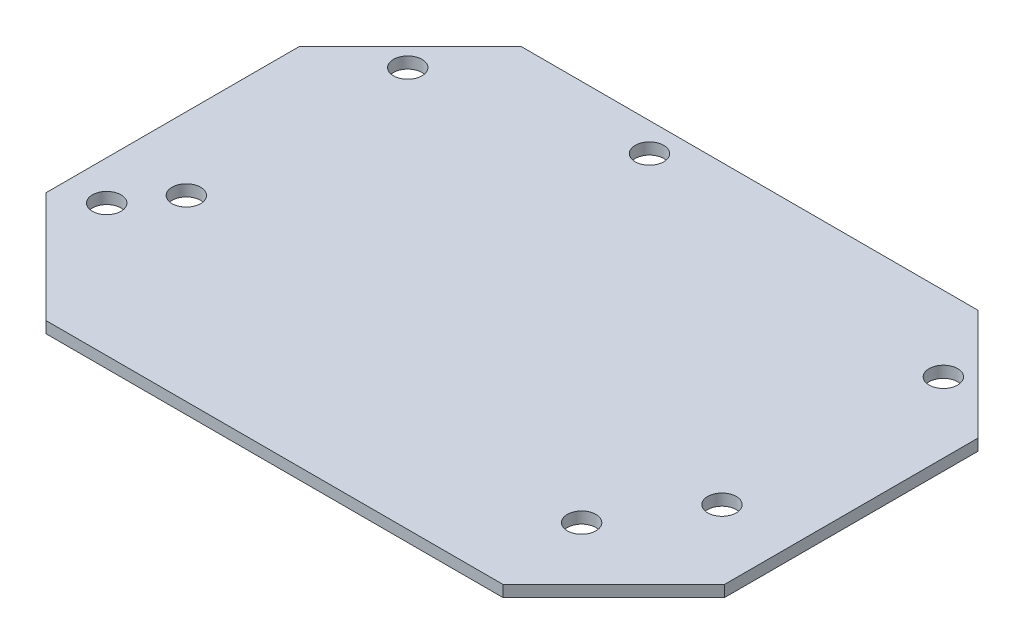
SolidWorks part; units mm, degrees
material "A-Glass Fiber"
ref_plane "Front Plane" through (0, 0, 0) normal (0, 0, 1) x (1, 0, 0)
ref_plane "Top Plane" through (0, 0, 0) normal (0, 1, 0) x (1, 0, 0)
ref_plane "Right Plane" through (0, 0, 0) normal (1, 0, 0) x (0, 0, -1)
sketch "Sketch1" plane through (0, 0, 0) normal (0, 1, 0) x (1, 0, 0)
  line L0 (0, 15.5) -> (15.5, 0)
  line L1 (15.5, 0) -> (79.5, 0)
  line L2 (0, 15.5) -> (0, 51)
  line L3 (15.5, 66.5) -> (79.5, 66.5)
  line L4 (95, 15.5) -> (95, 51)
  line L5 (0, 51) -> (15.5, 66.5)
  line L6 (95, 51) -> (79.5, 66.5)
  line L7 (95, 15.5) -> (79.5, 0)
  point P12 (0, 0)
  point P13 (75.943, 0)
  point P14 (72.7748, 77.1835)
  dimension "D1" = 66.5
  dimension "D2" = 95
  dimension "D3" = 15.5
  dimension "D4" = 135
  dimension "D5" = 135
  dimension "D6" = 135
  dimension "D7" = 15.5
  dimension "D8" = 15.5
  dimension "D9" = 15.5
extrude "Boss-Extrude1" add sketch "Sketch1" along normal blind 1.6 contours L0 L1 L7 L4 L6 L3 L5 L2
sketch "Sketch2" plane through (0, 1.6, 0) normal (0, 1, 0) x (1, 0, 0)
  line L0 (15.5, 0) -> (79.5, 0) construction
  line L1 (0, 15.5) -> (0, 51) construction
  circle A0 centre (5.5, 18.5) radius 2
  circle A1 centre (77.5, 13) radius 2
  circle A2 centre (37.5, 62.5) radius 2
  dimension "D1" = 4
  dimension "D2" = 4
  dimension "D3" = 4
  dimension "D4" = 5.5
  dimension "D5" = 18.5
  dimension "D6" = 13
  dimension "D7" = 77.5
  dimension "D8" = 62.5
  dimension "D9" = 37.5
extrude "Cut-Extrude1" cut sketch "Sketch2" against normal through all
sketch "Sketch3" plane through (0, 1.6, 0) normal (0, 1, 0) x (1, 0, 0)
  circle A0 centre (10.15, 56) radius 2
  circle A1 centre (85.15, 56) radius 2
  circle A2 centre (85.15, 25) radius 2
  circle A3 centre (10.15, 25) radius 2
  dimension "D1" = 4
  dimension "D2" = 4
  dimension "D3" = 4
  dimension "D4" = 4
extrude "Cut-Extrude2" cut sketch "Sketch3" against normal up to next
